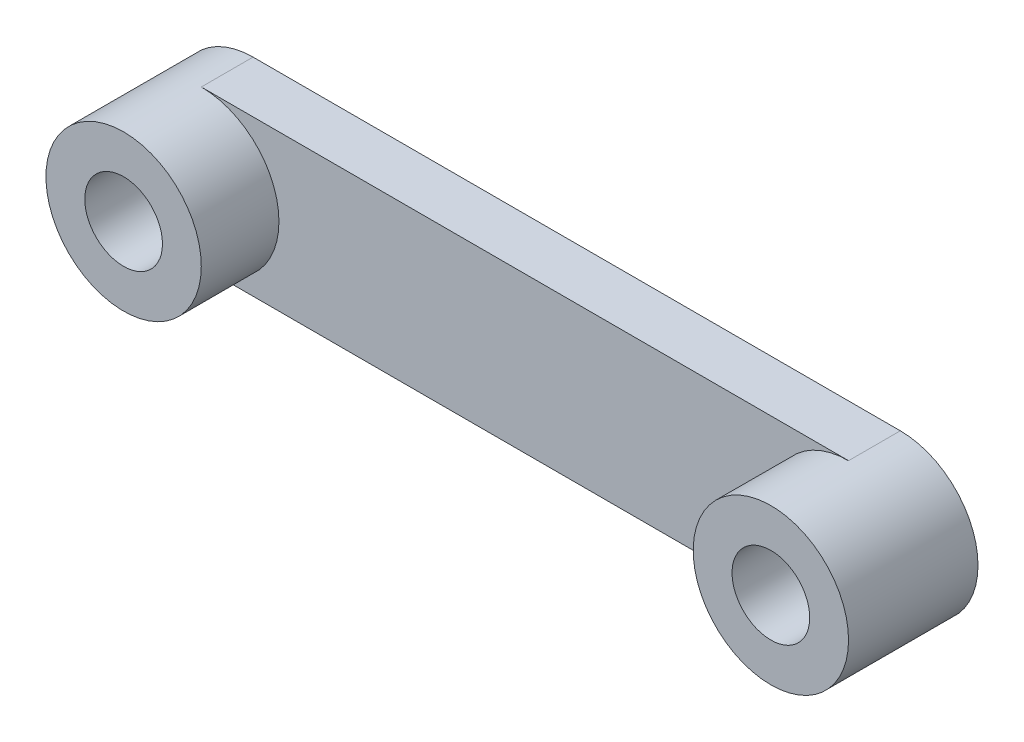
SolidWorks part; units mm, degrees
ref_plane "Front" through (0, 0, 0) normal (0, 0, 1) x (1, 0, 0)
ref_plane "Top" through (0, 0, 0) normal (0, 1, 0) x (1, 0, 0)
ref_plane "Right" through (0, 0, 0) normal (1, 0, 0) x (0, 0, -1)
sketch "Эскиз1" plane through (0, 0, 0) normal (0, 0, 1) x (1, 0, 0)
  line L0 (-25.494, 0) -> (25.0677, 0) construction
  line L1 (0, 7.3112) -> (0, -10.3104) construction
  line L2 (-12.5, 3) -> (12.5, 3)
  line L3 (-12.5, -3) -> (12.5, -3)
  circle A0 centre (-12.5, 0) radius 1.5
  circle A1 centre (12.5, 0) radius 1.5
  circle A2 centre (-12.5, 0) radius 3
  circle A3 centre (12.5, 0) radius 3
  dimension "D1" = 3
  dimension "D3" = 6
  dimension "D2" = 25
extrude "Бобышка-Вытянуть1" add sketch "Эскиз1" along normal mid plane 2 contours A3 L2 A2 L3 | A3 A1 | A0 | A2 region at (0, 0, 0) region at (14.5613, 2.0613, 0) region at (-12.5, 0, 0)
extrude "Бобышка-Вытянуть3" add sketch "Эскиз1<4>" along normal blind 4 contours A3 A1 | A2 A0 region at (-10.4387, 2.0613, 0) region at (14.5613, 2.0613, 0)
sketch "Эскиз1<4>" plane through (0, 0, 0) normal (0, 0, 1) x (1, 0, 0) same geometry as "Эскиз1"
